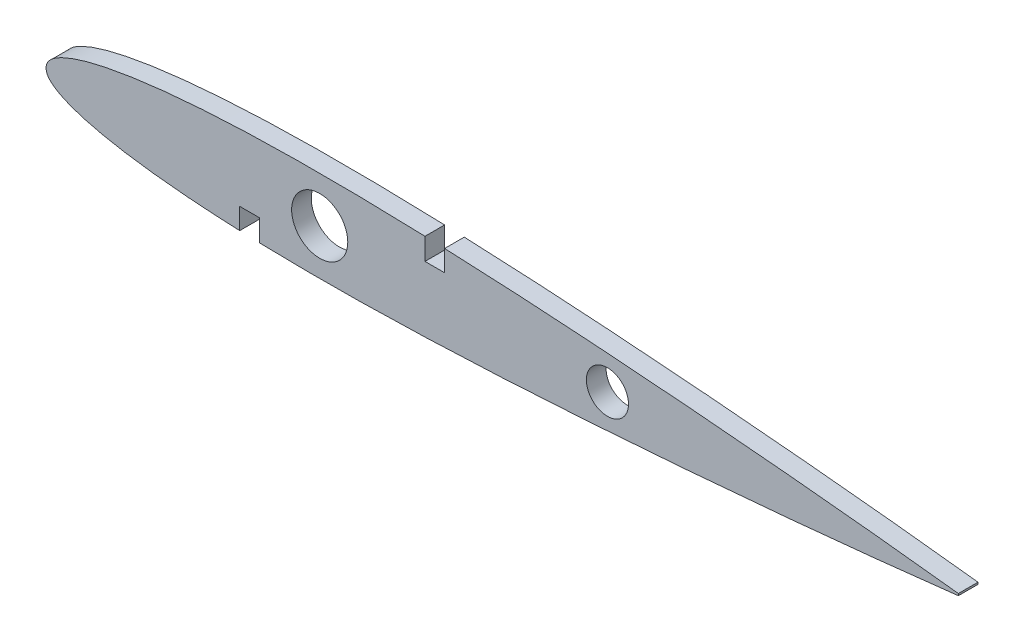
SolidWorks part; units mm, degrees
material "Фанера"
ref_plane "Спереди" through (0, 0, 0) normal (0, 0, 1) x (1, 0, 0)
ref_plane "Сверху" through (0, 0, 0) normal (0, 1, 0) x (1, 0, 0)
ref_plane "Справа" through (0, 0, 0) normal (1, 0, 0) x (0, 0, -1)
curve "Кривая1"
  spline degree 3 poles (200, 0.1365, 0) (199.688, 0.1729, 0) (198.8167, 0.2745, 0) (197.2359, 0.4561, 0) (195.145, 0.6923, 0) (192.7015, 0.9625, 0) (189.9816, 1.2561, 0) (187.0365, 1.566, 0) (183.905, 1.8867, 0) (180.6179, 2.2137, 0) (177.2012, 2.5436, 0) (173.6771, 2.8733, 0) (170.065, 3.2002, 0) (166.3822, 3.5221, 0) (162.6444, 3.8368, 0) (158.8659, 4.1424, 0) (155.06, 4.437, 0) (151.2387, 4.7189, 0) (147.4135, 4.9862, 0) (143.595, 5.2374, 0) (139.7935, 5.4706, 0) (136.0183, 5.6841, 0) (132.2786, 5.8765, 0) (128.5831, 6.0459, 0) (124.94, 6.191, 0) (121.3572, 6.3103, 0) (117.8424, 6.4025, 0) (114.4029, 6.4663, 0) (111.0457, 6.5008, 0) (107.7777, 6.505, 0) (104.6056, 6.4782, 0) (101.5356, 6.4201, 0) (98.5742, 6.3302, 0) (95.7272, 6.2086, 0) (93.0006, 6.0555, 0) (90.4002, 5.8711, 0) (87.9314, 5.6561, 0) (85.5998, 5.4114, 0) (83.4106, 5.1378, 0) (81.3691, 4.8365, 0) (79.4802, 4.5088, 0) (77.7488, 4.156, 0) (76.1798, 3.7796, 0) (74.7776, 3.3811, 0) (73.5467, 2.9618, 0) (72.4905, 2.523, 0) (71.6134, 2.0657, 0) (70.9148, 1.5895, 0) (70.4055, 1.0913, 0) (70.0654, 0.5615, 0) (70.0211, 0.181, 0) (70, 0, 0) knots 0 0 0 0 0.007145 0.019956 0.036196 0.055011 0.075879 0.098429 0.122376 0.147488 0.173572 0.20046 0.228005 0.256076 0.284555 0.313333 0.34231 0.371393 0.400496 0.429538 0.458442 0.487136 0.515552 0.543624 0.57129 0.598491 0.62517 0.651272 0.676746 0.701542 0.725611 0.748908 0.771388 0.793008 0.813728 0.833508 0.85231 0.870097 0.886836 0.902493 0.917037 0.930441 0.94268 0.953734 0.96359 0.972247 0.979722 0.986065 0.991385 0.995901 1 1 1 1
curve "Кривая2"
  spline degree 3 poles (70, 0, 0) (70.0211, -0.181, 0) (70.0654, -0.5615, 0) (70.4055, -1.0913, 0) (70.9148, -1.5895, 0) (71.6134, -2.0657, 0) (72.4905, -2.523, 0) (73.5467, -2.9618, 0) (74.7776, -3.3811, 0) (76.1798, -3.7796, 0) (77.7488, -4.156, 0) (79.4802, -4.5088, 0) (81.3691, -4.8365, 0) (83.4106, -5.1378, 0) (85.5998, -5.4114, 0) (87.9314, -5.6561, 0) (90.4002, -5.8711, 0) (93.0006, -6.0555, 0) (95.7272, -6.2086, 0) (98.5742, -6.3302, 0) (101.5356, -6.4201, 0) (104.6056, -6.4782, 0) (107.7777, -6.505, 0) (111.0457, -6.5008, 0) (114.4029, -6.4663, 0) (117.8424, -6.4025, 0) (121.3572, -6.3103, 0) (124.94, -6.191, 0) (128.5831, -6.0459, 0) (132.2786, -5.8765, 0) (136.0183, -5.6841, 0) (139.7935, -5.4706, 0) (143.595, -5.2374, 0) (147.4135, -4.9862, 0) (151.2387, -4.7189, 0) (155.06, -4.437, 0) (158.8659, -4.1424, 0) (162.6444, -3.8368, 0) (166.3822, -3.5221, 0) (170.065, -3.2002, 0) (173.6771, -2.8733, 0) (177.2012, -2.5436, 0) (180.6179, -2.2137, 0) (183.905, -1.8867, 0) (187.0365, -1.566, 0) (189.9816, -1.2561, 0) (192.7015, -0.9625, 0) (195.145, -0.6923, 0) (197.2359, -0.4561, 0) (198.8167, -0.2745, 0) (199.688, -0.1729, 0) (200, -0.1365, 0) knots 0 0 0 0 0.004099 0.008615 0.013935 0.020278 0.027753 0.03641 0.046266 0.05732 0.069559 0.082963 0.097507 0.113164 0.129903 0.14769 0.166492 0.186272 0.206992 0.228612 0.251092 0.274389 0.298458 0.323254 0.348728 0.37483 0.401509 0.42871 0.456376 0.484448 0.512864 0.541558 0.570462 0.599504 0.628607 0.65769 0.686667 0.715445 0.743924 0.771995 0.79954 0.826428 0.852512 0.877624 0.901571 0.924121 0.944989 0.963804 0.980044 0.992855 1 1 1 1
sketch "Эскиз1" plane through (0, 0, 0) normal (0, 0, 1) x (1, 0, 0)
  line L0 (200, 0.1365) -> (200, -0.1365)
  line L1 (100.4, -6.3839) -> (100.4, -3.2866)
  line L2 (100.4, -3.2866) -> (97.6, -3.2866)
  line L3 (97.6, -3.2866) -> (97.6, -6.2866)
  line L4 (124, 6.2207) -> (124, 3.116)
  line L5 (124, 3.116) -> (126.8, 3.116)
  line L6 (126.8, 3.116) -> (126.8, 6.116)
  circle A0 centre (109, 0) radius 4
  arc A1 (150, 4.8046) -> (150, -4.8046) centre (150, 0) ccw
  arc A2 (142.9507, 5.2753) -> (142.9507, -5.2753) centre (150, 0) ccw
  circle A4 centre (150, 0) radius 3
  spline S0 degree 3 poles (-2794.2878, -889.5298) (135.735, 36.6932) (65.8249, 6.0454) (70.4055, -1.0913) (70.9148, -1.5895) (71.6134, -2.0657) (72.4905, -2.523) (73.5467, -2.9618) (74.7776, -3.3811) (76.1798, -3.7796) (77.7488, -4.156) (79.4802, -4.5088) (81.3691, -4.8365) (83.4106, -5.1378) (85.5998, -5.4114) (87.9314, -5.6561) (90.4002, -5.8711) (93.0006, -6.0555) (95.7272, -6.2086) (98.5742, -6.3302) (101.5356, -6.4201) (104.6056, -6.4782) (107.7777, -6.505) (111.0457, -6.5008) (114.4029, -6.4663) (117.8424, -6.4025) (121.3572, -6.3103) (124.94, -6.191) (128.5831, -6.0459) (132.2786, -5.8765) (136.0183, -5.6841) (139.7935, -5.4706) (143.595, -5.2374) (147.4135, -4.9862) (151.2387, -4.7189) (155.06, -4.437) (158.8659, -4.1424) (162.6444, -3.8368) (166.3822, -3.5221) (170.065, -3.2002) (174.8191, -2.7699) (179.4417, -2.3307) (183.905, -1.8867) (187.0365, -1.566) (189.9816, -1.2561) (192.7015, -0.9625) (195.145, -0.6923) (197.2359, -0.4561) (276.563, 8.6571) (353.7675, 29.8587) (777.5475, -2938.4018) knots -0.173769 -0.173769 -0.173769 -0.173769 0.004099 0.008615 0.013935 0.020278 0.027753 0.03641 0.046266 0.05732 0.069559 0.082963 0.097507 0.113164 0.129903 0.14769 0.166492 0.186272 0.206992 0.228612 0.251092 0.274389 0.298458 0.323254 0.348728 0.37483 0.401509 0.42871 0.456376 0.484448 0.512864 0.541558 0.570462 0.599504 0.628607 0.65769 0.686667 0.715445 0.743924 0.771995 0.79954 0.852512 0.877624 0.901571 0.924121 0.944989 0.963804 0.980044 0.992855 2.780207 2.780207 2.780207 2.780207 only from (70, 0) to (200, -0.1365) construction
  spline S1 degree 3 poles (777.5457, 2938.3893) (353.7673, -29.8586) (276.5629, -8.657) (197.2359, 0.4561) (195.145, 0.6923) (192.7015, 0.9625) (189.9816, 1.2561) (187.0365, 1.566) (183.905, 1.8867) (179.4417, 2.3307) (174.8191, 2.7699) (170.065, 3.2002) (166.3822, 3.5221) (162.6444, 3.8368) (158.8659, 4.1424) (155.06, 4.437) (151.2387, 4.7189) (147.4135, 4.9862) (143.595, 5.2374) (139.7935, 5.4706) (136.0183, 5.6841) (132.2786, 5.8765) (128.5831, 6.0459) (124.94, 6.191) (121.3572, 6.3103) (117.8424, 6.4025) (114.4029, 6.4663) (111.0457, 6.5008) (107.7777, 6.505) (104.6056, 6.4782) (101.5356, 6.4201) (98.5742, 6.3302) (95.7272, 6.2086) (93.0006, 6.0555) (90.4002, 5.8711) (87.9314, 5.6561) (85.5998, 5.4114) (83.4106, 5.1378) (81.3691, 4.8365) (79.4802, 4.5088) (77.7488, 4.156) (76.1798, 3.7796) (74.7776, 3.3811) (73.5467, 2.9618) (72.4905, 2.523) (71.6134, 2.0657) (70.9148, 1.5895) (70.4055, 1.0913) (65.8251, -6.0451) (135.7293, -36.6906) (-2793.9197, 889.4134) knots -1.780204 -1.780204 -1.780204 -1.780204 0.007145 0.019956 0.036196 0.055011 0.075879 0.098429 0.122376 0.147488 0.20046 0.228005 0.256076 0.284555 0.313333 0.34231 0.371393 0.400496 0.429538 0.458442 0.487136 0.515552 0.543624 0.57129 0.598491 0.62517 0.651272 0.676746 0.701542 0.725611 0.748908 0.771388 0.793008 0.813728 0.833508 0.85231 0.870097 0.886836 0.902493 0.917037 0.930441 0.94268 0.953734 0.96359 0.972247 0.979722 0.986065 0.991385 0.995901 1.173762 1.173762 1.173762 1.173762 only from (200, 0.1365) to (70, 0) construction
  spline S2 degree 3 poles (70, 0) (70.0211, -0.181) (70.0654, -0.5615) (70.4055, -1.0913) (70.9148, -1.5895) (71.6134, -2.0657) (72.4905, -2.523) (73.5467, -2.9618) (74.7776, -3.3811) (76.1798, -3.7796) (77.7488, -4.156) (79.4802, -4.5088) (81.3691, -4.8365) (83.4106, -5.1378) (85.5998, -5.4114) (87.9314, -5.6561) (90.4002, -5.8711) (93.0006, -6.0555) (95.4152, -6.1911) (96.9625, -6.2607) (97.6, -6.2866) knots 0 0 0 0 0.004099 0.008615 0.013935 0.020278 0.027753 0.03641 0.046266 0.05732 0.069559 0.082963 0.097507 0.113164 0.129903 0.14769 0.166492 0.186272 0.206992 0.221505 0.221505 0.221505 0.221505
  spline S3 degree 3 poles (200, 0.1365) (199.688, 0.1729) (198.8167, 0.2745) (197.2359, 0.4561) (195.145, 0.6923) (192.7015, 0.9625) (189.9816, 1.2561) (187.0365, 1.566) (183.905, 1.8867) (179.4417, 2.3307) (174.8191, 2.7699) (170.065, 3.2002) (166.3822, 3.5221) (162.6444, 3.8368) (158.8659, 4.1424) (155.06, 4.437) (151.2387, 4.7189) (147.4135, 4.9862) (143.595, 5.2374) (139.7935, 5.4706) (136.0183, 5.6841) (132.2786, 5.8765) (129.2098, 6.0172) (127.3884, 6.0925) (126.8, 6.116) knots 0 0 0 0 0.007145 0.019956 0.036196 0.055011 0.075879 0.098429 0.122376 0.147488 0.20046 0.228005 0.256076 0.284555 0.313333 0.34231 0.371393 0.400496 0.429538 0.458442 0.487136 0.515552 0.543624 0.55702 0.55702 0.55702 0.55702
  spline S4 degree 3 poles (100.4, -6.3839) (100.7666, -6.3946) (102.157, -6.4319) (104.6056, -6.4782) (107.7777, -6.505) (111.0457, -6.5008) (114.4029, -6.4663) (117.8424, -6.4025) (121.3572, -6.3103) (124.94, -6.191) (128.5831, -6.0459) (132.2786, -5.8765) (136.0183, -5.6841) (139.7935, -5.4706) (143.595, -5.2374) (147.4135, -4.9862) (151.2387, -4.7189) (155.06, -4.437) (158.8659, -4.1424) (162.6444, -3.8368) (166.3822, -3.5221) (170.065, -3.2002) (174.8191, -2.7699) (179.4417, -2.3307) (183.905, -1.8867) (187.0365, -1.566) (189.9816, -1.2561) (192.7015, -0.9625) (195.145, -0.6923) (197.2359, -0.4561) (198.8167, -0.2745) (199.688, -0.1729) (200, -0.1365) knots 0.242749 0.242749 0.242749 0.242749 0.251092 0.274389 0.298458 0.323254 0.348728 0.37483 0.401509 0.42871 0.456376 0.484448 0.512864 0.541558 0.570462 0.599504 0.628607 0.65769 0.686667 0.715445 0.743924 0.771995 0.79954 0.852512 0.877624 0.901571 0.924121 0.944989 0.963804 0.980044 0.992855 1 1 1 1
  spline S5 degree 3 poles (124, 6.2207) (123.1115, 6.2516) (121.0507, 6.3184) (117.8424, 6.4025) (114.4029, 6.4663) (111.0457, 6.5008) (107.7777, 6.505) (104.6056, 6.4782) (101.5356, 6.4201) (98.5742, 6.3302) (95.7272, 6.2086) (93.0006, 6.0555) (90.4002, 5.8711) (87.9314, 5.6561) (85.5998, 5.4114) (83.4106, 5.1378) (81.3691, 4.8365) (79.4802, 4.5088) (77.7488, 4.156) (76.1798, 3.7796) (74.7776, 3.3811) (73.5467, 2.9618) (72.4905, 2.523) (71.6134, 2.0657) (70.9148, 1.5895) (70.4055, 1.0913) (70.0654, 0.5615) (70.0211, 0.181) (70, 0) knots 0.578266 0.578266 0.578266 0.578266 0.598491 0.62517 0.651272 0.676746 0.701542 0.725611 0.748908 0.771388 0.793008 0.813728 0.833508 0.85231 0.870097 0.886836 0.902493 0.917037 0.930441 0.94268 0.953734 0.96359 0.972247 0.979722 0.986065 0.991385 0.995901 1 1 1 1
  point P13 (99, -3.2866)
  dimension "D1" = 8
  dimension "D11" = 4.8046
  dimension "D12" = 8.8046
  dimension "D13" = 6
  dimension "D2" = 39
  dimension "D8" = 2.8
  dimension "D9" = 10
  dimension "D3" = 3
  dimension "D4" = 2.8
  dimension "D5" = 15
  dimension "D6" = 3
  dimension "D10" = 80
  dimension "D7" = 9.6092
extrude "Бобышка-Вытянуть1" add sketch "Эскиз1" along normal mid plane 2.8 contours L4 S5 S2 L3 L2 L1 S4 A2 S3 L6 L5 A0 | A2 S4 A1 S3 | A1 S4 L0 S3 A4 region at (166.9016, 0, 0) region at (144.1337, 0, 0) region at (140.4544, 0, 0)
equation "\"D11@Эскиз1\"=\"D7@Эскиз1\"/2"
equation "\"D12@Эскиз1\"=\"D11@Эскиз1\"+4"
